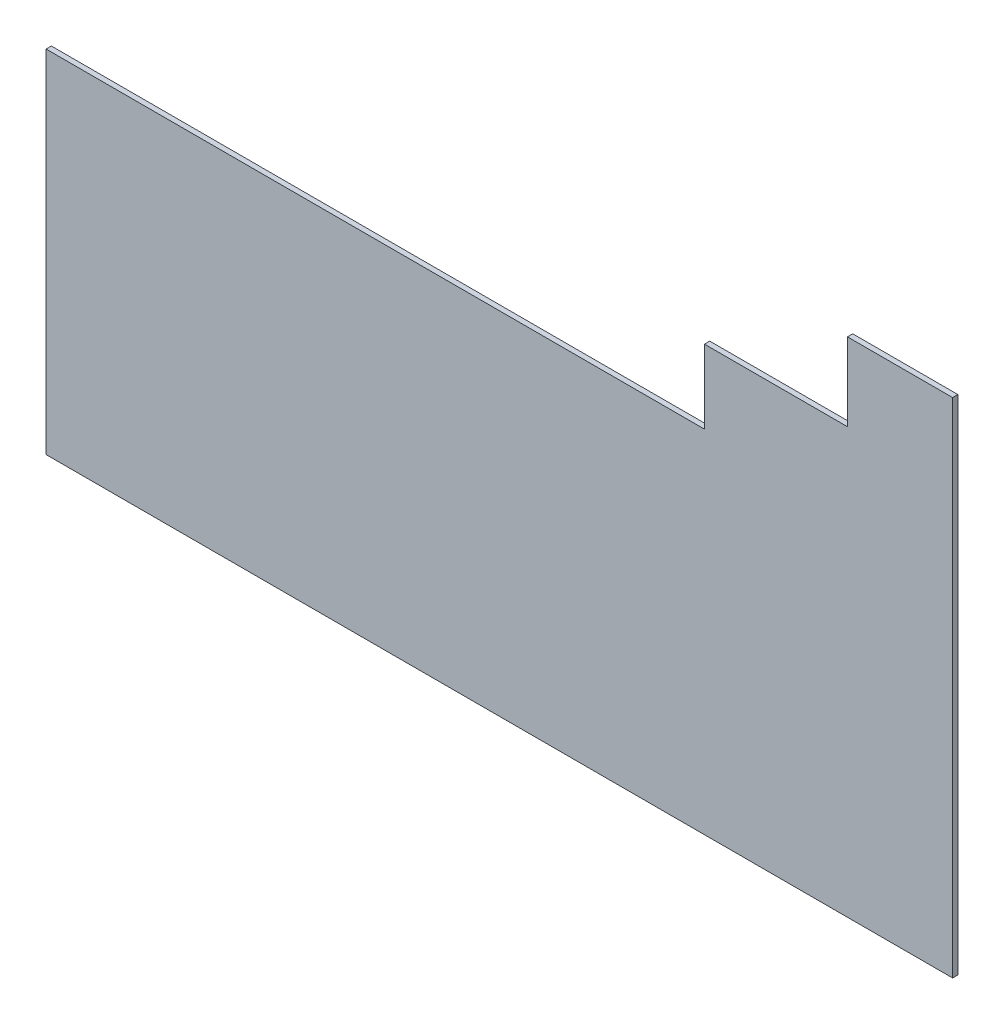
SolidWorks part; units mm, degrees
ref_plane "Ön Düzlem" through (0, 0, 0) normal (0, 0, 1) x (1, 0, 0)
ref_plane "Üst Düzlem" through (0, 0, 0) normal (0, 1, 0) x (1, 0, 0)
ref_plane "Sağ Düzlem" through (0, 0, 0) normal (1, 0, 0) x (0, 0, -1)
sketch "Çizim1" plane through (0, 0, 0) normal (0, 0, 1) x (1, 0, 0)
  line L0 (0, 0) -> (0, 1895)
  line L1 (2935, 2020) -> (4900, 2020)
  line L2 (4900, 2020) -> (4900, 2515)
  line L3 (4900, 2515) -> (6002, 2515)
  line L4 (6002, 2515) -> (6002, 0)
  line L5 (6002, 0) -> (0, 0)
  line L8 (2935, 2020) -> (2935, 1895)
  line L9 (2935, 1895) -> (0, 1895)
  dimension "D1" = 125
  dimension "D2" = 620
  dimension "D3" = 2935
  dimension "D4" = 495
  dimension "D5" = 1102
  dimension "D6" = 2020
  dimension "D7" = 2515
  dimension "D8" = 6002
  dimension "D9" = 1965
  dimension "D10" = 4900
base flange "Taban-Flanş1" sketch "Çizim1" thickness 25 reverse thickness direction no parameters "D1"=8
sketch "Çizim6" plane through (0, 0, -25) normal (0, 0, -1) x (-1, 0, 0)
  line L1 (-4900, 2515) -> (0, 2515)
  line L2 (-4900, 2515) -> (-4900, 2020)
  line L3 (-4900, 2020) -> (0, 2020)
  line L4 (0, 2515) -> (0, 2020)
  line L5 (-2935, 1895) -> (0, 1895) construction
  line L6 (-2935, 2020) -> (-2935, 1895) construction
  dimension "D1" = 4900
  dimension "D2" = 495
  dimension "D3" = 125
  dimension "D4" = 2935
sketch "Çizim7" plane through (0, 0, 0) normal (0, 0, 1) x (1, 0, 0)
  line L0 (0, 0) -> (6002, 0) construction
  line L1 (0, 1895) -> (1400, 1895)
  line L2 (0, 1895) -> (0, 0)
  line L3 (0, 0) -> (1400, 0)
  line L4 (1400, 1895) -> (1400, 0)
  line L5 (2935, 2020) -> (2935, 1895) construction
  line L6 (4900, 2020) -> (2935, 2020) construction
  line L7 (4900, 2515) -> (5210, 2515)
  line L8 (4900, 2515) -> (4900, 2020)
  line L9 (4900, 2020) -> (5210, 2020)
  line L10 (5210, 2515) -> (5210, 2020)
  line L11 (6002, 0) -> (6002, 2515) construction
  dimension "D1" = 1535
  dimension "D2" = 1400
  dimension "D3" = 1895
  dimension "D4" = 2275
  dimension "D5" = 310
  dimension "D6" = 495
  dimension "D7" = 792
extrude "Kes-Ekstrüzyon1" cut sketch "Çizim7" against normal through all both and the other way through all
sketch "Çizim8" plane through (0, 0, 0) normal (0, 0, 1) x (1, 0, 0)
  line L0 (1400, 0) -> (6002, 0) construction
  line L1 (6002, 2515) -> (5710, 2515)
  line L2 (6002, 2515) -> (6002, 0)
  line L3 (6002, 0) -> (5710, 0)
  line L4 (5710, 2515) -> (5710, 0)
  line L5 (5210, 2515) -> (5210, 2020) construction
  dimension "D1" = 500
  dimension "D2" = 2515
  dimension "D3" = 292
extrude "Kes-Ekstrüzyon2" cut sketch "Çizim8" against normal through all both and the other way through all
sketch "Çizim10" plane through (0, 0, 0) normal (0, 0, 1) x (1, 0, 0)
  line L0 (5210, 2020) -> (2935, 2020) construction
  line L1 (4300, 2020) -> (1400, 2020)
  line L2 (4300, 2020) -> (4300, 1670)
  line L3 (4300, 1670) -> (1400, 1670)
  line L4 (1400, 2020) -> (1400, 1670)
  line L5 (1400, 1895) -> (1400, 0) construction
  line L6 (1400, 0) -> (5710, 0) construction
  line L7 (2935, 2020) -> (2935, 1895) construction
  line L8 (2935, 1895) -> (1400, 1895) construction
  line L9 (5210, 2515) -> (5210, 2020) construction
  dimension "D1" = 2900
  dimension "D2" = 1670
  dimension "D3" = 1365
  dimension "D4" = 225
  dimension "D5" = 910
  dimension "D6" = 350
  dimension "D7" = 1535
extrude "Kes-Ekstrüzyon3" cut sketch "Çizim10" against normal through all both and the other way through all
sketch "Çizim11" plane through (0, 0, 0) normal (0, 0, 1) x (1, 0, 0)
  line L0 (4300, 1670) -> (4530, 1670)
  line L1 (4530, 1670) -> (4530, 2020)
  line L2 (4530, 2020) -> (5210, 2020)
  line L3 (5210, 2020) -> (5210, 2390)
  line L4 (5210, 2515) -> (5210, 2020) construction
  line L5 (5210, 2390) -> (5710, 2390)
  line L6 (5710, 0) -> (5710, 2515) construction
  line L7 (1400, 1670) -> (1400, 0) construction
  line L8 (4300, 1670) -> (4300, 2199.5523)
  line L9 (4300, 2199.5523) -> (4530, 2199.5523)
  line L10 (4530, 2199.5523) -> (5189.2317, 2697.2667)
  line L11 (5189.2317, 2697.2667) -> (5749.8153, 2697.2667)
  line L12 (5749.8153, 2697.2667) -> (5778.6304, 2406.4967)
  line L13 (5778.6304, 2406.4967) -> (5710, 2390)
  dimension "D1" = 3130
  dimension "D2" = 350
  dimension "D3" = 680
  dimension "D4" = 370
  dimension "D5" = 500
extrude "Kes-Ekstrüzyon4" cut sketch "Çizim11" against normal through all both and the other way through all
sketch "Büküm-Çizgileri1" [suppressed] plane through (0, 0, 0) normal (0, 1, 0) x (1, 0, 0)
sketch "Sınırlandırma-Kutusu1" [suppressed] plane through (0, 0, 0) normal (0, 1, 0) x (1, 0, 0)
sheet metal parameters "Sac-Levha1" thickness 25 parameters "D1"=8
flat pattern "Düz-Çoğaltma1" [suppressed]
sketch "Büküm-Çizgileri2" plane through (0, 0, 0) normal (0, 1, 0) x (1, 0, 0)
sketch3d "Sınırlandırma-Kutusu2" [suppressed]
  line L0 (0, 0, 0) -> (6002, 0, 0) construction
  line L1 (0, 2515, 0) -> (6002, 2515, 0) construction
  line L2 (0, 0, 0) -> (0, 2515, 0) construction
  line L3 (6002, 0, 0) -> (6002, 2515, 0) construction
sketch "Çizim6-1" [suppressed] plane through (0, 0, -25) normal (0, 0, -1) x (-1, 0, 0)
  line L1 (-4900, 2515) -> (0, 2515)
  line L2 (-4900, 2515) -> (-4900, 2020)
  line L3 (-4900, 2020) -> (0, 2020)
  line L4 (0, 2515) -> (0, 2020)
  line L5 (-2935, 1895) -> (0, 1895) construction
  line L6 (-2935, 2020) -> (-2935, 1895) construction
  dimension "D1" = 4900
  dimension "D2" = 495
  dimension "D3" = 125
  dimension "D4" = 2935
sheet metal parameters "Sac-Levha2" thickness 25 parameters "D1"=8
flat pattern "Düz-Çoğaltma1" [suppressed]
sketch "Büküm-Çizgileri2" plane through (0, 0, 0) normal (0, 1, 0) x (1, 0, 0)
sketch3d "Sınırlandırma-Kutusu2" [suppressed]
  line L0 (1400, 0, 0) -> (6002, 0, 0) construction
  line L1 (1400, 2515, 0) -> (6002, 2515, 0) construction
  line L2 (1400, 0, 0) -> (1400, 2515, 0) construction
  line L3 (6002, 0, 0) -> (6002, 2515, 0) construction
sketch "Çizim6-1" [suppressed] plane through (0, 0, -25) normal (0, 0, -1) x (-1, 0, 0)
  line L1 (-4900, 2515) -> (0, 2515)
  line L2 (-4900, 2515) -> (-4900, 2020)
  line L3 (-4900, 2020) -> (0, 2020)
  line L4 (0, 2515) -> (0, 2020)
  line L5 (-2935, 1895) -> (-1400, 1895) construction
  line L6 (-2935, 2020) -> (-2935, 1895) construction
  dimension "D1" = 4900
  dimension "D2" = 495
  dimension "D3" = 125
  dimension "D4" = 2935
sketch "Çizim6-2" [suppressed] plane through (0, 0, -25) normal (0, 0, -1) x (-1, 0, 0)
  line L1 (-4900, 2515) -> (0, 2515)
  line L2 (-4900, 2515) -> (-4900, 2020)
  line L3 (-4900, 2020) -> (0, 2020)
  line L4 (0, 2515) -> (0, 2020)
  line L5 (-2935, 1895) -> (-1400, 1895) construction
  line L6 (-2935, 2020) -> (-2935, 1895) construction
  dimension "D1" = 4900
  dimension "D2" = 495
  dimension "D3" = 125
  dimension "D4" = 2935
sketch "Çizim6-3" [suppressed] plane through (0, 0, -25) normal (0, 0, -1) x (-1, 0, 0)
  line L1 (-4900, 2515) -> (0, 2515)
  line L2 (-4900, 2515) -> (-4900, 2020)
  line L3 (-4900, 2020) -> (0, 2020)
  line L4 (0, 2515) -> (0, 2020)
  line L5 (-2935, 1895) -> (-1400, 1895) construction
  line L6 (-2935, 2020) -> (-2935, 1895) construction
  dimension "D1" = 4900
  dimension "D2" = 495
  dimension "D3" = 125
  dimension "D4" = 2935
sheet metal parameters "Sac-Levha3" thickness 25 parameters "D1"=8
flat pattern "Düz-Çoğaltma1" [suppressed]
sketch "Büküm-Çizgileri2" plane through (0, 0, 0) normal (0, 1, 0) x (1, 0, 0)
sketch3d "Sınırlandırma-Kutusu2" [suppressed]
  line L0 (1400, 0, 0) -> (5710, 0, 0) construction
  line L1 (1400, 2515, 0) -> (5710, 2515, 0) construction
  line L2 (1400, 0, 0) -> (1400, 2515, 0) construction
  line L3 (5710, 0, 0) -> (5710, 2515, 0) construction
sketch "Çizim6-1" [suppressed] plane through (0, 0, -25) normal (0, 0, -1) x (-1, 0, 0)
  line L1 (-4900, 2515) -> (0, 2515)
  line L2 (-4900, 2515) -> (-4900, 2020)
  line L3 (-4900, 2020) -> (0, 2020)
  line L4 (0, 2515) -> (0, 2020)
  line L5 (-2935, 1895) -> (-1400, 1895) construction
  line L6 (-2935, 2020) -> (-2935, 1895) construction
  dimension "D1" = 4900
  dimension "D2" = 495
  dimension "D3" = 125
  dimension "D4" = 2935
sketch "Çizim6-2" [suppressed] plane through (0, 0, -25) normal (0, 0, -1) x (-1, 0, 0)
  line L1 (-4900, 2515) -> (0, 2515)
  line L2 (-4900, 2515) -> (-4900, 2020)
  line L3 (-4900, 2020) -> (0, 2020)
  line L4 (0, 2515) -> (0, 2020)
  line L5 (-2935, 1895) -> (-1400, 1895)
  line L6 (-2935, 2020) -> (-2935, 1895)
  dimension "D1" = 4900
  dimension "D2" = 495
  dimension "D3" = 125
  dimension "D4" = 2935
sketch "Çizim6-3" [suppressed] plane through (0, 0, -25) normal (0, 0, -1) x (-1, 0, 0)
  line L1 (-4900, 2515) -> (0, 2515)
  line L2 (-4900, 2515) -> (-4900, 2020)
  line L3 (-4900, 2020) -> (0, 2020)
  line L4 (0, 2515) -> (0, 2020)
  line L5 (-2935, 1895) -> (-1400, 1895)
  line L6 (-2935, 2020) -> (-2935, 1895)
  dimension "D1" = 4900
  dimension "D2" = 495
  dimension "D3" = 125
  dimension "D4" = 2935
sketch "Çizim6-4" [suppressed] plane through (0, 0, -25) normal (0, 0, -1) x (-1, 0, 0)
  line L1 (-4900, 2515) -> (0, 2515)
  line L2 (-4900, 2515) -> (-4900, 2020)
  line L3 (-4900, 2020) -> (0, 2020)
  line L4 (0, 2515) -> (0, 2020)
  line L5 (-2935, 1895) -> (-1400, 1895) construction
  line L6 (-2935, 2020) -> (-2935, 1895) construction
  dimension "D1" = 4900
  dimension "D2" = 495
  dimension "D3" = 125
  dimension "D4" = 2935
sketch "Çizim6-5" [suppressed] plane through (0, 0, -25) normal (0, 0, -1) x (-1, 0, 0)
  line L1 (-4900, 2515) -> (0, 2515)
  line L2 (-4900, 2515) -> (-4900, 2020)
  line L3 (-4900, 2020) -> (0, 2020)
  line L4 (0, 2515) -> (0, 2020)
  line L5 (-2935, 1895) -> (-1400, 1895) construction
  line L6 (-2935, 2020) -> (-2935, 1895) construction
  dimension "D1" = 4900
  dimension "D2" = 495
  dimension "D3" = 125
  dimension "D4" = 2935
sheet metal parameters "Sac-Levha4" thickness 25 parameters "D1"=8
flat pattern "Düz-Çoğaltma1" [suppressed]
sketch "Büküm-Çizgileri2" plane through (0, 0, 0) normal (0, 1, 0) x (1, 0, 0)
sketch3d "Sınırlandırma-Kutusu2" [suppressed]
  line L0 (1400, 0, 0) -> (5710, 0, 0) construction
  line L1 (1400, 2515, 0) -> (5710, 2515, 0) construction
  line L2 (1400, 0, 0) -> (1400, 2515, 0) construction
  line L3 (5710, 0, 0) -> (5710, 2515, 0) construction
sketch "Çizim6-1" [suppressed] plane through (0, 0, -25) normal (0, 0, -1) x (-1, 0, 0)
  line L1 (-4900, 2515) -> (0, 2515)
  line L2 (-4900, 2515) -> (-4900, 2020)
  line L3 (-4900, 2020) -> (0, 2020)
  line L4 (0, 2515) -> (0, 2020)
  line L5 (-2935, 1895) -> (0, 1895) construction
  line L6 (-2935, 2020) -> (-2935, 1895) construction
  dimension "D1" = 4900
  dimension "D2" = 495
  dimension "D3" = 125
  dimension "D4" = 2935
sketch "Çizim6-2" [suppressed] plane through (0, 0, -25) normal (0, 0, -1) x (-1, 0, 0)
  line L1 (-4900, 2515) -> (0, 2515)
  line L2 (-4900, 2515) -> (-4900, 2020)
  line L3 (-4900, 2020) -> (0, 2020)
  line L4 (0, 2515) -> (0, 2020)
  line L5 (-2935, 1895) -> (-1400, 1895)
  line L6 (-2935, 2020) -> (-2935, 1895)
  dimension "D1" = 4900
  dimension "D2" = 495
  dimension "D3" = 125
  dimension "D4" = 2935
sketch "Çizim6-3" [suppressed] plane through (0, 0, -25) normal (0, 0, -1) x (-1, 0, 0)
  line L1 (-4900, 2515) -> (0, 2515)
  line L2 (-4900, 2515) -> (-4900, 2020)
  line L3 (-4900, 2020) -> (0, 2020)
  line L4 (0, 2515) -> (0, 2020)
  line L5 (-2935, 1895) -> (-1400, 1895)
  line L6 (-2935, 2020) -> (-2935, 1895)
  dimension "D1" = 4900
  dimension "D2" = 495
  dimension "D3" = 125
  dimension "D4" = 2935
sketch "Çizim6-4" [suppressed] plane through (0, 0, -25) normal (0, 0, -1) x (-1, 0, 0)
  line L1 (-4900, 2515) -> (0, 2515)
  line L2 (-4900, 2515) -> (-4900, 2020)
  line L3 (-4900, 2020) -> (0, 2020)
  line L4 (0, 2515) -> (0, 2020)
  line L5 (-2935, 1895) -> (-1400, 1895)
  line L6 (-2935, 2020) -> (-2935, 1895)
  dimension "D1" = 4900
  dimension "D2" = 495
  dimension "D3" = 125
  dimension "D4" = 2935
sketch "Çizim6-5" [suppressed] plane through (0, 0, -25) normal (0, 0, -1) x (-1, 0, 0)
  line L1 (-4900, 2515) -> (0, 2515)
  line L2 (-4900, 2515) -> (-4900, 2020)
  line L3 (-4900, 2020) -> (0, 2020)
  line L4 (0, 2515) -> (0, 2020)
  line L5 (-2935, 1895) -> (-1400, 1895)
  line L6 (-2935, 2020) -> (-2935, 1895)
  dimension "D1" = 4900
  dimension "D2" = 495
  dimension "D3" = 125
  dimension "D4" = 2935
sketch "Çizim6-6" [suppressed] plane through (0, 0, -25) normal (0, 0, -1) x (-1, 0, 0)
  line L1 (-4900, 2515) -> (0, 2515)
  line L2 (-4900, 2515) -> (-4900, 2020)
  line L3 (-4900, 2020) -> (0, 2020)
  line L4 (0, 2515) -> (0, 2020)
  line L5 (-2935, 1895) -> (0, 1895) construction
  line L6 (-2935, 2020) -> (-2935, 1895) construction
  dimension "D1" = 4900
  dimension "D2" = 495
  dimension "D3" = 125
  dimension "D4" = 2935
sheet metal parameters "Sac-Levha5" thickness 25 parameters "D1"=8
flat pattern "Düz-Çoğaltma1" [suppressed]
sketch "Büküm-Çizgileri2" plane through (0, 0, 0) normal (0, 1, 0) x (1, 0, 0)
sketch3d "Sınırlandırma-Kutusu2" [suppressed]
  line L0 (1400, 0, 0) -> (5710, 0, 0) construction
  line L1 (1400, 2390, 0) -> (5710, 2390, 0) construction
  line L2 (1400, 0, 0) -> (1400, 2390, 0) construction
  line L3 (5710, 0, 0) -> (5710, 2390, 0) construction
sketch "Çizim6-1" plane through (0, 0, -25) normal (0, 0, -1) x (-1, 0, 0)
  line L1 (-4900, 2515) -> (0, 2515)
  line L2 (-4900, 2515) -> (-4900, 2020)
  line L3 (-4900, 2020) -> (0, 2020)
  line L4 (0, 2515) -> (0, 2020)
  line L5 (-2935, 1895) -> (0, 1895) construction
  line L6 (-2935, 2020) -> (-2935, 1895) construction
  dimension "D1" = 4900
  dimension "D2" = 495
  dimension "D3" = 125
  dimension "D4" = 2935
sketch "Çizim6-2" [suppressed] plane through (0, 0, -25) normal (0, 0, -1) x (-1, 0, 0)
  line L1 (-4900, 2515) -> (0, 2515)
  line L2 (-4900, 2515) -> (-4900, 2020)
  line L3 (-4900, 2020) -> (0, 2020)
  line L4 (0, 2515) -> (0, 2020)
  line L5 (-2935, 1895) -> (-1400, 1895)
  line L6 (-2935, 2020) -> (-2935, 1895)
  dimension "D1" = 4900
  dimension "D2" = 495
  dimension "D3" = 125
  dimension "D4" = 2935
sketch "Çizim6-3" [suppressed] plane through (0, 0, -25) normal (0, 0, -1) x (-1, 0, 0)
  line L1 (-4900, 2515) -> (0, 2515)
  line L2 (-4900, 2515) -> (-4900, 2020)
  line L3 (-4900, 2020) -> (0, 2020)
  line L4 (0, 2515) -> (0, 2020)
  line L5 (-2935, 1895) -> (-1400, 1895)
  line L6 (-2935, 2020) -> (-2935, 1895)
  dimension "D1" = 4900
  dimension "D2" = 495
  dimension "D3" = 125
  dimension "D4" = 2935
sketch "Çizim6-4" [suppressed] plane through (0, 0, -25) normal (0, 0, -1) x (-1, 0, 0)
  line L1 (-4900, 2515) -> (0, 2515)
  line L2 (-4900, 2515) -> (-4900, 2020)
  line L3 (-4900, 2020) -> (0, 2020)
  line L4 (0, 2515) -> (0, 2020)
  line L5 (-2935, 1895) -> (-1400, 1895)
  line L6 (-2935, 2020) -> (-2935, 1895)
  dimension "D1" = 4900
  dimension "D2" = 495
  dimension "D3" = 125
  dimension "D4" = 2935
sketch "Çizim6-5" [suppressed] plane through (0, 0, -25) normal (0, 0, -1) x (-1, 0, 0)
  line L1 (-4900, 2515) -> (0, 2515)
  line L2 (-4900, 2515) -> (-4900, 2020)
  line L3 (-4900, 2020) -> (0, 2020)
  line L4 (0, 2515) -> (0, 2020)
  line L5 (-2935, 1895) -> (-1400, 1895)
  line L6 (-2935, 2020) -> (-2935, 1895)
  dimension "D1" = 4900
  dimension "D2" = 495
  dimension "D3" = 125
  dimension "D4" = 2935
sketch "Çizim6-6" [suppressed] plane through (0, 0, -25) normal (0, 0, -1) x (-1, 0, 0)
  line L1 (-4900, 2515) -> (0, 2515)
  line L2 (-4900, 2515) -> (-4900, 2020)
  line L3 (-4900, 2020) -> (0, 2020)
  line L4 (0, 2515) -> (0, 2020)
  line L5 (-2935, 1895) -> (0, 1895)
  line L6 (-2935, 2020) -> (-2935, 1895)
  dimension "D1" = 4900
  dimension "D2" = 495
  dimension "D3" = 125
  dimension "D4" = 2935
sketch "Çizim6-7" [suppressed] plane through (0, 0, -25) normal (0, 0, -1) x (-1, 0, 0)
  line L1 (-4900, 2515) -> (0, 2515)
  line L2 (-4900, 2515) -> (-4900, 2020)
  line L3 (-4900, 2020) -> (0, 2020)
  line L4 (0, 2515) -> (0, 2020)
  line L5 (-2935, 1895) -> (0, 1895) construction
  line L6 (-2935, 2020) -> (-2935, 1895) construction
  dimension "D1" = 4900
  dimension "D2" = 495
  dimension "D3" = 125
  dimension "D4" = 2935
